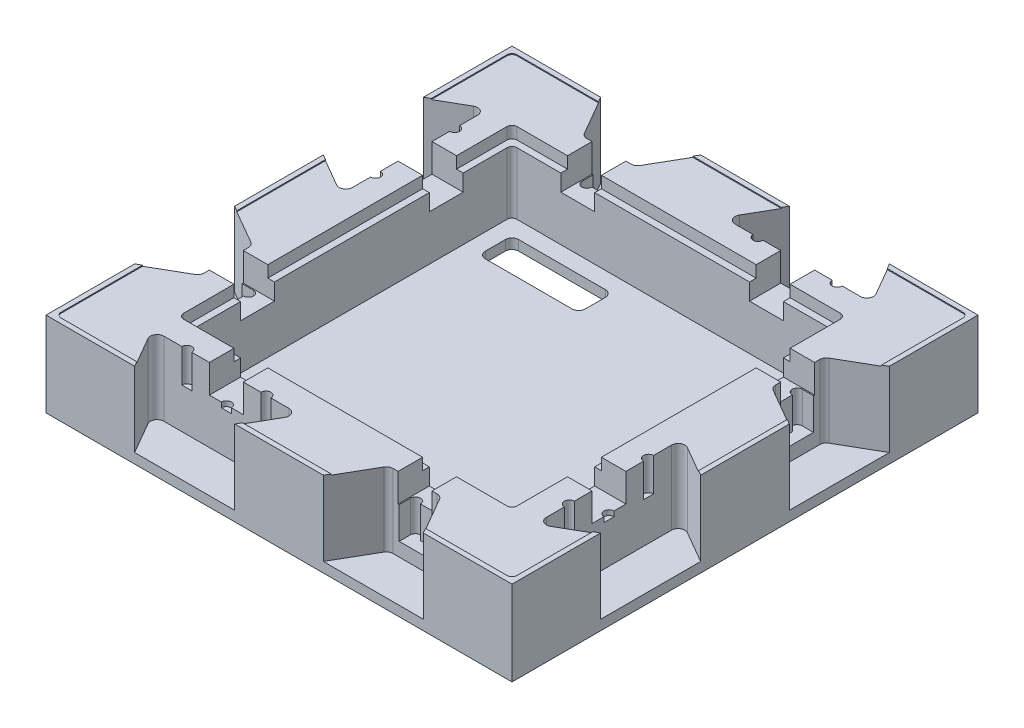
SolidWorks part; units mm, degrees
material "Macor"
ref_plane "Front Plane" through (0, 0, 0) normal (0, 0, 1) x (1, 0, 0)
ref_plane "Top Plane" through (0, 0, 0) normal (0, 1, 0) x (1, 0, 0)
ref_plane "Right Plane" through (0, 0, 0) normal (1, 0, 0) x (0, 0, -1)
sketch "Sketch1" plane through (0, 0, 0) normal (0, 1, 0) x (1, 0, 0)
  line L1 (-69.85, -69.85) -> (69.85, -69.85)
  line L2 (-69.85, -69.85) -> (-69.85, 69.85)
  line L3 (-69.85, 69.85) -> (69.85, 69.85)
  line L4 (69.85, -69.85) -> (69.85, 69.85)
  line L5 (-69.85, -69.85) -> (69.85, 69.85) construction
  line L6 (-69.85, 69.85) -> (69.85, -69.85) construction
  point P0 (0, 0)
  dimension "D1" = 139.7
extrude "Boss-Extrude1" add sketch "Sketch1" along normal mid plane 25.4
sketch "Sketch2" plane through (0, 12.7, 0) normal (0, 1, 0) x (1, 0, 0)
  line L0 (69.85, -69.85) -> (69.85, 69.85) construction
  line L1 (-68.35, -68.35) -> (68.35, -68.35)
  line L2 (-68.35, -68.35) -> (-68.35, 68.35)
  line L3 (-68.35, 68.35) -> (68.35, 68.35)
  line L4 (68.35, -68.35) -> (68.35, 68.35)
  line L5 (-68.35, -68.35) -> (68.35, 68.35) construction
  line L6 (-68.35, 68.35) -> (68.35, -68.35) construction
  point P0 (0, 0)
  dimension "D1" = 1.5
extrude "Cut-Extrude1" cut sketch "Sketch2" against normal offset from surface (0.3 mm away) 0.3 up to face at (0, 12.7, 0)
sketch "Sketch4" plane through (0, 12.7, 0) normal (0, 1, 0) x (1, 0, 0)
  line L0 (-43.2833, -69.85) -> (-50.5002, -57.35)
  line L1 (-69.85, -69.85) -> (69.85, -69.85) construction
  line L2 (-50.5002, -57.35) -> (-6.0665, -57.35)
  line L3 (-6.0665, -57.35) -> (-13.2833, -69.85)
  line L4 (-13.2833, -69.85) -> (-43.2833, -69.85)
  line L5 (43.2833, -69.85) -> (36.0665, -57.35)
  line L24 (43.2833, -69.85) -> (13.2833, -69.85)
  line L25 (-69.85, -69.85) -> (-43.2833, -69.85) construction
  line L26 (-13.2833, -69.85) -> (13.2833, -69.85) construction
  line L27 (43.2833, -69.85) -> (69.85, -69.85) construction
  line L28 (36.0665, -57.35) -> (20.5002, -57.35)
  line L30 (13.2833, -69.85) -> (20.5002, -57.35)
  dimension "D2" = 30
  dimension "D1" = 60
  dimension "D3" = 12.5
  dimension "D4" = 60
extrude "Cut-Extrude2" cut sketch "Sketch4" against normal offset from surface 3 and the other way through all up to face at (0, -12.7, 0)
sketch "Sketch6" plane through (0, 12.4, 0) normal (0, 1, 0) x (1, 0, 0)
  line L0 (-50.5002, -57.35) -> (-6.0665, -57.35) construction
  line L1 (-6.0665, -57.35) -> (-50.5002, -57.35) construction
  line L2 (-50.5002, -57.35) -> (-41.6418, -57.35) construction
  line L3 (-38.6418, -57.35) -> (-29.7833, -57.35) construction
  line L4 (-26.7833, -57.35) -> (-17.9249, -57.35) construction
  line L5 (-14.9249, -57.35) -> (-6.0665, -57.35) construction
  line L6 (-41.6418, -57.35) -> (-38.6418, -57.35)
  line L7 (-29.7833, -57.35) -> (-26.7833, -57.35)
  line L8 (-17.9249, -57.35) -> (-14.9249, -57.35)
  arc A0 (-41.6418, -57.35) -> (-38.6418, -57.35) centre (-40.1418, -57.35) cw
  arc A1 (-29.7833, -57.35) -> (-26.7833, -57.35) centre (-28.2833, -57.35) cw
  arc A2 (-17.9249, -57.35) -> (-14.9249, -57.35) centre (-16.4249, -57.35) cw
  dimension "D1" = 1.5
  dimension "D2" = 8.8584
extrude "Cut-Extrude4" cut sketch "Sketch6" against normal blind 10
sketch "Sketch18" plane through (0, 0, 57.35) normal (0, 0, 1) x (1, 0, 0)
  line L1 (0, -13.97) -> (0, 13.97) construction
  line L3 (23.2033, 12.4) -> (23.2033, 3.92)
  line L4 (23.2033, 3.92) -> (33.3633, 3.92)
  line L5 (33.3633, 12.4) -> (33.3633, 3.92)
  line L6 (-23.2033, 12.4) -> (-33.3633, 12.4)
  line L7 (-33.3633, 12.4) -> (-33.3633, 3.92)
  line L8 (-23.2033, 12.4) -> (-23.2033, 3.92)
  line L9 (-23.2033, 3.92) -> (-33.3633, 3.92)
  line L10 (23.2033, 12.4) -> (33.3633, 12.4)
  line L11 (20.5002, 12.4) -> (36.0665, 12.4) construction
  point P7 (28.2833, 12.4)
  point P14 (28.2833, 12.4)
  dimension "D1" = 10.16
  dimension "D2" = 8.48
extrude "Cut-Extrude6" cut sketch "Sketch18" against normal blind 20
sketch "Sketch19" plane through (0, 0, 57.35) normal (0, 0, 1) x (1, 0, 0)
  line L1 (25.1083, 3.92) -> (31.4583, 3.92)
  line L2 (25.1083, 3.92) -> (25.1083, -2.43)
  line L3 (25.1083, -2.43) -> (31.4583, -2.43)
  line L4 (31.4583, 3.92) -> (31.4583, -2.43)
  line L5 (23.2033, 3.92) -> (33.3633, 3.92) construction
  point P7 (28.2833, 3.92)
  point P8 (28.2833, 3.92)
  dimension "D1" = 6.35
extrude "Cut-Extrude7" [suppressed] cut sketch "Sketch19" against normal blind 1.7875
sketch "Sketch20" [suppressed] plane through (0, 0, 57.35) normal (0, 0, 1) x (1, 0, 0)
  line L0 (25.1083, 7.525) -> (25.1083, 1.175) construction
  line L2 (24.3082, 7.525) -> (24.3082, 1.175)
  line L3 (24.3082, 1.175) -> (32.2584, 1.175)
  line L4 (32.2584, 7.525) -> (32.2584, 1.175)
  line L6 (25.1083, 1.175) -> (31.4583, 1.175) construction
  line L10 (32.2584, 7.525) -> (24.3082, 7.525)
  point P9 (28.2833, 1.175)
  point P11 (28.2833, 1.175)
  dimension "D1" = 7.9502
extrude "Cut-Extrude8" [suppressed] cut sketch "Sketch20" against normal blind 1.0001
sketch "Sketch22" plane through (0, 0, 57.35) normal (0, 0, 1) x (1, 0, 0)
  line L0 (23.2033, 3.92) -> (33.3633, 3.92) construction
  line L1 (23.5208, 3.92) -> (33.0458, 3.92)
  line L2 (23.5208, 3.92) -> (23.5208, -5.605)
  line L3 (23.5208, -5.605) -> (33.0458, -5.605)
  line L4 (33.0458, 3.92) -> (33.0458, -5.605)
  point P6 (28.2833, 3.92)
  point P7 (28.2833, 3.92)
  dimension "D1" = 9.525
extrude "Cut-Extrude10" cut sketch "Sketch22" against normal blind 3.375
sketch "Sketch23" plane through (0, 3.92, 0) normal (0, 1, 0) x (1, 0, 0)
  line L0 (33.0458, -53.975) -> (23.5208, -53.975) construction
  circle A0 centre (25.0208, -53.975) radius 1.5
  circle A1 centre (31.5458, -53.975) radius 1.5
  dimension "D1" = 3
extrude "Cut-Extrude11" cut sketch "Sketch23" against normal up to surface (9.525 mm away) up to face at (28.2833, -5.605, 55.6625)
ref_axis "Axis1" through (0, 29.6009, 0) along (0, -1, 0)
fillet "Fillet1" radius 1.5 4 edges at (-68.35, 12.55, 68.35) (68.35, 12.55, 68.35) (68.35, 12.55, -68.35) (-68.35, 12.55, -68.35)
fillet "Fillet3" radius 2 4 edges at (-50.5002, 1.35, 57.35) (-6.0665, 1.35, 57.35) (20.5002, 1.35, 57.35) (36.0665, 1.35, 57.35) tangent propagation no
pattern_circular "CirPattern1" count 4 over 360 about axis through (0, 29.6009, 0) along (0, -1, 0) of "Cut-Extrude2", "Fillet3", "Cut-Extrude4", "Cut-Extrude10", "Cut-Extrude11"
sketch "Sketch13" plane through (0, 12.4, 0) normal (0, 1, 0) x (1, 0, 0)
  line L1 (-50, -50) -> (50, -50)
  line L2 (-50, -50) -> (-50, 50)
  line L3 (-50, 50) -> (50, 50)
  line L4 (50, -50) -> (50, 50)
  line L5 (-50, -50) -> (50, 50) construction
  line L6 (-50, 50) -> (50, -50) construction
  arc A0 (-57.35, 38.6418) -> (-57.35, 41.6418) centre (-57.35, 40.1418) ccw construction
  arc A1 (-57.35, 38.6418) -> (-57.35, 41.6418) centre (-57.35, 40.1418) ccw construction
  point P0 (0, 0)
  point P9 (-55.85, 40.1418)
  dimension "D1" = 100
  dimension "D2" = 5.85
extrude "Cut-Extrude5" cut sketch "Sketch13" against normal offset from surface (22.1 mm away) 3 up to face at (0, -12.7, 0)
sketch "Sketch14" plane through (0, -9.7, 0) normal (0, 1, 0) x (1, 0, 0)
  line L1 (-50, -50) -> (50, -50)
  line L2 (-50, -50) -> (-50, 50)
  line L3 (-50, 50) -> (50, 50)
  line L4 (50, -50) -> (50, 50)
  line L5 (-50, -50) -> (50, 50) construction
  line L6 (-50, 50) -> (50, -50) construction
  line L7 (-48, -48) -> (48, -48)
  line L8 (-48, -48) -> (-48, 48)
  line L9 (-48, 48) -> (48, 48)
  line L10 (48, -48) -> (48, 48)
  line L11 (-48, -48) -> (48, 48) construction
  line L12 (-48, 48) -> (48, -48) construction
  point P0 (0, 0)
  point P7 (0, 0)
  dimension "D1" = 96
extrude "Boss-Extrude2" add sketch "Sketch14" along normal offset from surface (18.6 mm away) 3.5 up to face at (0.8039, 12.4, -4.8855)
sketch "Sketch15" plane through (0, -9.7, 0) normal (0, 1, 0) x (1, 0, 0)
  line L5 (-5, -5) -> (5, -5)
  line L6 (-5, -5) -> (-5, 5)
  line L7 (-5, 5) -> (5, 5)
  line L8 (5, -5) -> (5, 5)
  line L9 (-5, -5) -> (5, 5) construction
  line L10 (-5, 5) -> (5, -5) construction
  point P0 (0, 0)
  dimension "D1" = 10
extrude "PCB_Support" [suppressed] add sketch "Sketch15" along normal up to surface (18.6 mm away)
sketch "Sketch16" plane through (0, -9.7, 0) normal (0, 1, 0) x (1, 0, 0)
  line L0 (-48, 48) -> (-48, -48) construction
  line L1 (-43, 43) -> (-13, 43)
  line L2 (-43, 43) -> (-43, 33)
  line L3 (-43, 33) -> (-13, 33)
  line L4 (-13, 43) -> (-13, 33)
  line L5 (-48, 48) -> (48, 48) construction
  dimension "D1" = 10
  dimension "D2" = 30
  dimension "D3" = 5
  dimension "D4" = 5
extrude "Vent_Sussy" cut sketch "Sketch16" against normal through all
pattern_circular "CirPattern5" count 2 over 360 about axis through (0, 29.6009, 0) along (0, -1, 0) of "Vent_Sussy"
fillet "Fillet4" radius 2 8 edges at (-43, -11.2, -33) (-43, -11.2, -43) (-13, -11.2, -43) (-13, -11.2, -33) (13, -11.2, 43) (13, -11.2, 33) (43, -11.2, 33) (43, -11.2, 43)
fillet "Fillet5" radius 1.5 8 edges at (50, 10.65, -50) (50, 10.65, 50) (-50, 10.65, 50) (-50, 10.65, -50) (48, -0.4, -48) (-48, -0.4, -48) (48, -0.4, 48) (-48, -0.4, 48)
sketch "Sketch17" plane through (0, -12.7, 0) normal (0, -1, 0) x (1, 0, 0)
  line L0 (-69.85, 69.85) -> (69.85, 69.85) construction
  line L1 (69.85, -69.85) -> (49.85, -69.85)
  line L2 (69.85, -69.85) -> (69.85, 69.85)
  line L3 (69.85, 69.85) -> (49.85, 69.85)
  line L4 (49.85, -69.85) -> (49.85, 69.85)
  line L6 (-69.85, -69.85) -> (-49.85, -69.85)
  line L7 (-69.85, -69.85) -> (-69.85, 69.85)
  line L8 (-69.85, 69.85) -> (-49.85, 69.85)
  line L9 (-49.85, -69.85) -> (-49.85, 69.85)
  circle A0 centre (0, 0) radius 25
  dimension "D2" = 50
  dimension "D1" = 20
split line "Split Line1"
pattern_circular "CirPattern4" count 4 over 360 about axis through (0, 29.6009, 0) along (0, -1, 0) of "Cut-Extrude6"
sketch "Sketch21" plane through (0, 0, 50) normal (0, 0, 1) x (1, 0, 0)
  line L1 (23.2033, 3.92) -> (33.3633, 3.92)
  line L2 (23.2033, 3.92) -> (23.2033, 8.9)
  line L3 (23.2033, 8.9) -> (33.3633, 8.9)
  line L4 (33.3633, 3.92) -> (33.3633, 8.9)
  line L5 (-23.2033, 8.9) -> (-33.3633, 8.9)
  line L6 (-23.2033, 8.9) -> (-23.2033, 3.92)
  line L7 (-23.2033, 3.92) -> (-33.3633, 3.92)
  line L8 (-33.3633, 8.9) -> (-33.3633, 3.92)
extrude "Cut-Extrude9" cut sketch "Sketch21" against normal up to surface (2 mm away) up to face at (0, -0.4, 48)
equation "\"panel_width\"= 5.5in"
equation "\"finger_joint_width\"= 30mm"
equation "\"D1@Sketch1\"=\"panel_width\""
equation "\"D2@Sketch4\"=\"finger_joint_width\""
